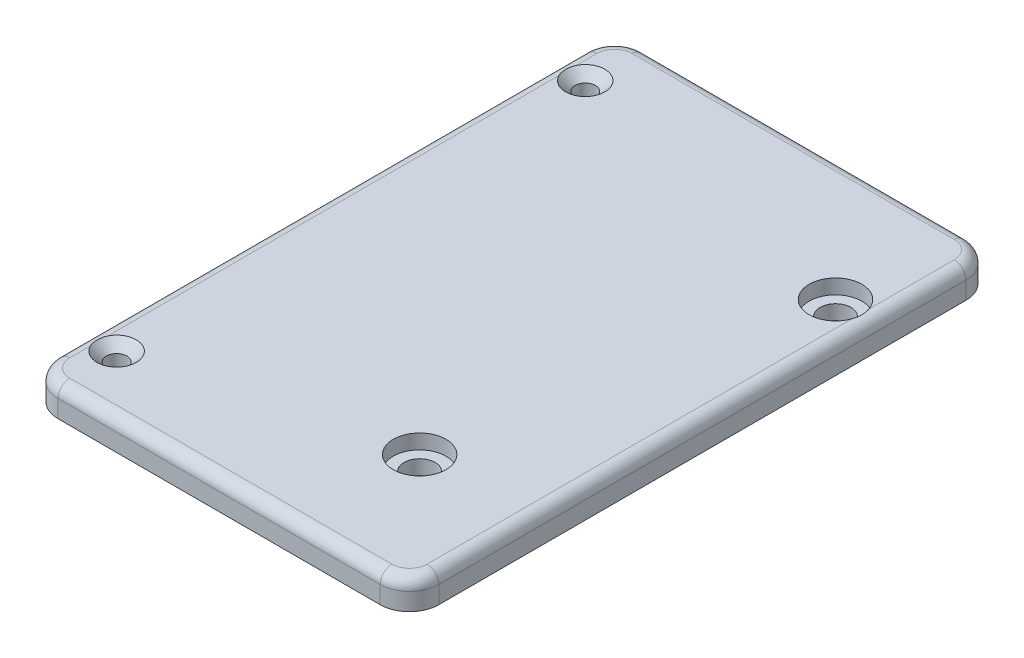
SolidWorks part; units mm, degrees
ref_plane "Front Plane" through (0, 0, 0) normal (0, 0, 1) x (1, 0, 0)
ref_plane "Top Plane" through (0, 0, 0) normal (0, 1, 0) x (1, 0, 0)
ref_plane "Right Plane" through (0, 0, 0) normal (1, 0, 0) x (0, 0, -1)
sketch "Sketch2" plane through (0, 0, 0) normal (0, 1, 0) x (1, 0, 0)
  line L1 (-32.5, 50) -> (32.5, 50)
  line L2 (-32.5, 50) -> (-32.5, -50)
  line L3 (-32.5, -50) -> (32.5, -50)
  line L4 (32.5, 50) -> (32.5, -50)
  line L5 (-32.5, 50) -> (32.5, -50) construction
  line L6 (-32.5, -50) -> (32.5, 50) construction
  circle A0 centre (-27.5, 40) radius 1.75
  circle A1 centre (-27.5, -40) radius 1.75
  circle A2 centre (26.23, 29) radius 2.65
  circle A3 centre (13.65, -29.42) radius 2.65
  point P0 (0, 0)
  dimension "D3" = 3.5
  dimension "D4" = 5
  dimension "D8" = 5.3
  dimension "D9" = 5.3
  dimension "D1" = 65
  dimension "D2" = 100
  dimension "D5" = 5
  dimension "D6" = 10
  dimension "D7" = 10
  dimension "D10" = 18.85
  dimension "D11" = 20.58
  dimension "D12" = 6.27
  dimension "D13" = 21
extrude "Boss-Extrude1" add sketch "Sketch2" along normal blind 5
sketch "Sketch3" plane through (0, 5, 0) normal (0, 1, 0) x (1, 0, 0)
  circle A0 centre (26.23, 29) radius 4.5
  circle A1 centre (13.65, -29.42) radius 4.5
  dimension "D1" = 9
  dimension "D2" = 9
extrude "Cut-Extrude1" cut sketch "Sketch3" against normal blind 2.5
fillet "Fillet1" radius 5 4 edges at (32.5, 2.5, 50) (-32.5, 2.5, -50) (32.5, 2.5, -50) (-32.5, 2.5, 50)
chamfer "Chamfer1" distance 1.6 angle 45 2 edges at (-27.5, 5, 41.75) (-27.5, 5, -38.25)
fillet "Fillet2" radius 2 8 edges at (-31.0355, 5, 48.5355) (-32.5, 5, 0) (-31.0355, 5, -48.5355) (0, 5, -50) (31.0355, 5, -48.5355) (32.5, 5, 0) (31.0355, 5, 48.5355) (0, 5, 50)
